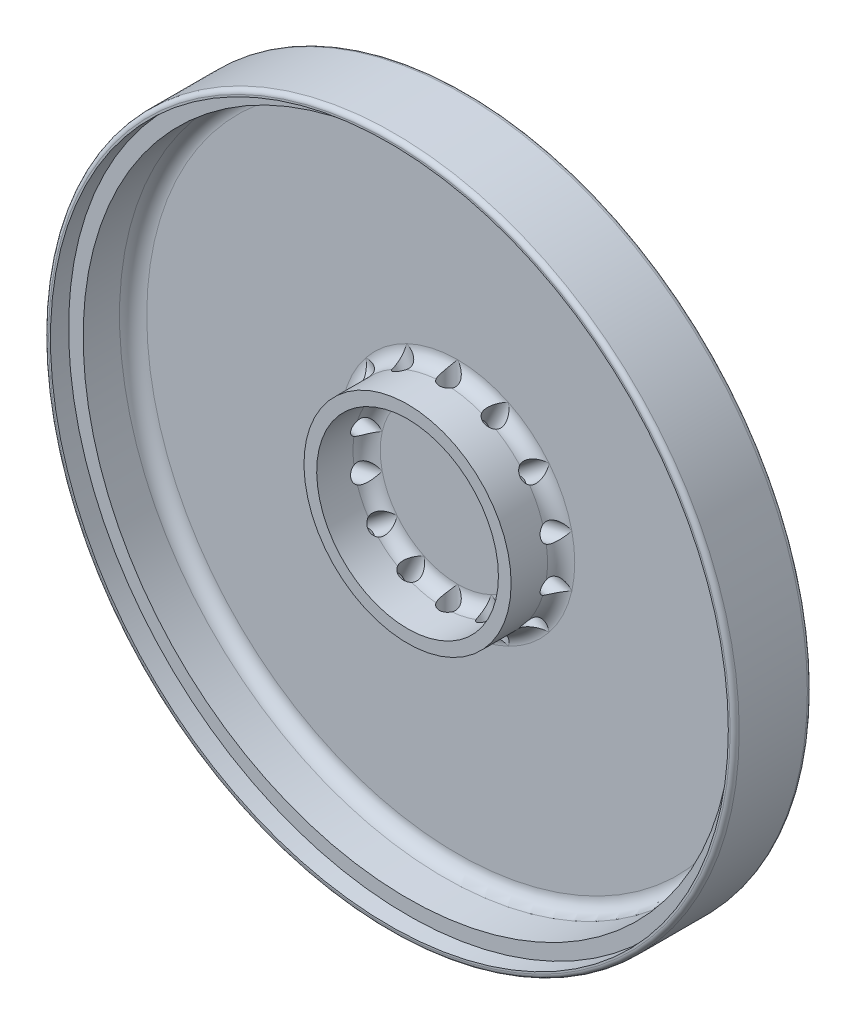
SolidWorks part; units mm, degrees
note: The reader was unsure of these and kept them because the rebuilt part matched: shared geometry of "Sketch1<3>", "Sketch1<4>", "Sketch1<5>".
ref_plane "Front Plane" through (0, 0, 0) normal (0, 0, 1) x (1, 0, 0)
ref_plane "Top Plane" through (0, 0, 0) normal (0, 1, 0) x (1, 0, 0)
ref_plane "Right Plane" through (0, 0, 0) normal (1, 0, 0) x (0, 0, -1)
sketch "Sketch1" plane through (0, 0, 0) normal (0, 0, 1) x (1, 0, 0)
  circle A0 centre (0, 0) radius 76
  circle A1 centre (0, 0) radius 74.6
  circle A2 centre (0, 0) radius 71.4
  circle A3 centre (0, 0) radius 20
  circle A4 centre (0, 0) radius 22.8
  dimension "D1" = 152
  dimension "D5" = 40
  dimension "D2" = 1.4
  dimension "D3" = 3.2
  dimension "D4" = 2.8
extrude "Boss-Extrude1" add sketch "Sketch1" against normal blind 2 contours A2 A4 | A1 A2 | A0 A1 | A3 | A4 A3
extrude "Boss-Extrude2" add sketch "Sketch1<3>" along normal blind 15 contours A0 A1
sketch "Sketch1<3>" plane through (0, 0, 0) normal (0, 0, 1) x (1, 0, 0) same geometry as "Sketch1"
extrude "Boss-Extrude3" add sketch "Sketch1<4>" along normal blind 11 contours A1 A2
sketch "Sketch1<4>" plane through (0, 0, 0) normal (0, 0, 1) x (1, 0, 0) same geometry as "Sketch1"
extrude "Boss-Extrude4" add sketch "Sketch1<5>" along normal blind 11 contours A4 A3
sketch "Sketch1<5>" plane through (0, 0, 0) normal (0, 0, 1) x (1, 0, 0) same geometry as "Sketch1"
sketch "Sketch2" plane through (0, 0, 0) normal (0, 1, 0) x (1, 0, 0)
  line L2 (-20, 0) -> (20, 0) construction
  circle A0 centre (0, -2) radius 2
  dimension "D1" = 4
extrude "Cut-Extrude3" cut sketch "Sketch2" against normal up to next and the other way up to next
fillet "Fillet1" radius 3 1 edges at (71.4, 0, 0)
fillet "Fillet2" radius 3 8 edges at (20, 0, 0) (-22.8, 0, 0) (-0.4514, 22.7955, 3.9484) (-0.4488, 19.995, 3.949) (-20, 0, 0) (22.8, 0, 0) (0, -22.8, 4) (0, -20, 4)
fillet "Fillet3" radius 1 1 edges at (76, 0, -2)
fillet "Fillet4" radius 1 1 edges at (76, 0, 15)
pattern_circular "CirPattern1" count 7 over 360 about axis through (0, 0, 11) along (0, 0, -1) of "Cut-Extrude3"
